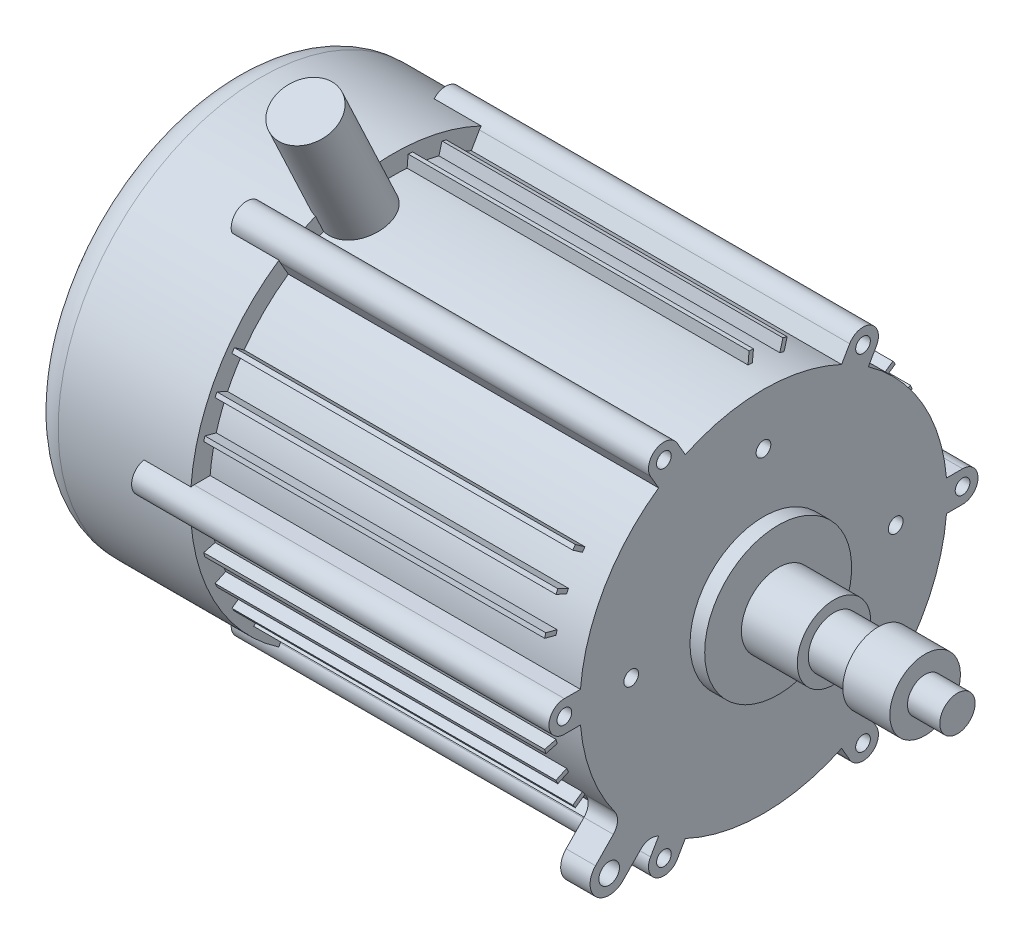
SolidWorks part; units mm, degrees
ref_plane "Спереди" through (0, 0, 0) normal (0, 0, 1) x (1, 0, 0)
ref_plane "Сверху" through (0, 0, 0) normal (0, 1, 0) x (1, 0, 0)
ref_plane "Справа" through (0, 0, 0) normal (1, 0, 0) x (0, 0, -1)
sketch "Эскиз1" plane through (0, 0, 0) normal (0, 0, 1) x (1, 0, 0)
  line L0 (-1000, 0) -> (49000, 0) construction
  line L1 (-181, 0) -> (-181, 69)
  line L2 (-181, 69) -> (-126, 69)
  line L3 (-126, 69) -> (-126, 62.5)
  line L4 (-126, 62.5) -> (0, 62.5)
  line L5 (0, 62.5) -> (0, 25)
  line L6 (0, 25) -> (5, 25)
  line L7 (5, 25) -> (5, 12.5)
  line L8 (5, 12.5) -> (24, 12.5)
  line L9 (24, 12.5) -> (24, 8.75)
  line L10 (24, 8.75) -> (39, 8.75)
  line L11 (39, 8.75) -> (39, 12)
  line L12 (39, 12) -> (55, 12)
  line L13 (55, 12) -> (55, 6)
  line L14 (55, 6) -> (66, 6)
  line L15 (66, 6) -> (66, 0)
  line L16 (-181, 0) -> (66, 0)
  point P5 (132.9582, 6.3738)
  dimension "D1" = 138
  dimension "181" = 181
  dimension "D2" = 55
  dimension "D3" = 125
  dimension "D4" = 11
  dimension "D5" = 12
  dimension "D6" = 24
  dimension "D7" = 16
  dimension "D8" = 17.5
  dimension "D9" = 15
  dimension "D10" = 25
  dimension "D11" = 50
  dimension "D12" = 5
  dimension "D13" = 50
revolve "Повернуть1" add sketch "Эскиз1" angle 360 about L0
sketch "Эскиз2" plane through (0, 0, 0) normal (1, 0, 0) x (0, 0, -1)
  line L0 (0, 0) -> (0, 62.5) construction
  line L1 (0, 0) -> (31.25, 54.1266) construction
  line L2 (19.3284, 43.9777) -> (28.4216, 38.7277)
  line L3 (19.3284, 43.9777) -> (29.3284, 61.2982)
  line L4 (28.4216, 38.7277) -> (38.4216, 56.0482)
  line L6 (0, 0) -> (62.5, 0) construction
  line L7 (47.75, 5.25) -> (67.75, 5.25)
  line L8 (47.75, -5.25) -> (67.75, -5.25)
  line L9 (47.75, 5.25) -> (47.75, -5.25)
  line L10 (0, 0) -> (31.25, -54.1266) construction
  line L11 (28.4216, -38.7277) -> (38.4216, -56.0482)
  line L12 (19.3284, -43.9777) -> (29.3284, -61.2982)
  line L13 (28.4216, -38.7277) -> (19.3284, -43.9777)
  line L14 (0, 0) -> (-31.25, -54.1266) construction
  line L15 (-19.3284, -43.9777) -> (-29.3284, -61.2982)
  line L16 (-28.4216, -38.7277) -> (-38.4216, -56.0482)
  line L17 (-19.3284, -43.9777) -> (-28.4216, -38.7277)
  line L18 (0, 0) -> (-62.5, 0) construction
  line L19 (-47.75, -5.25) -> (-67.75, -5.25)
  line L20 (-47.75, 5.25) -> (-67.75, 5.25)
  line L21 (-47.75, -5.25) -> (-47.75, 5.25)
  line L22 (0, 0) -> (-31.25, 54.1266) construction
  line L23 (-28.4216, 38.7277) -> (-38.4216, 56.0482)
  line L24 (-19.3284, 43.9777) -> (-29.3284, 61.2982)
  line L25 (-28.4216, 38.7277) -> (-19.3284, 43.9777)
  circle A0 centre (0, 0) radius 62.5 construction
  circle A1 centre (0, 0) radius 62.5 construction
  arc A2 (38.4216, 56.0482) -> (29.3284, 61.2982) centre (33.875, 58.6732) ccw
  circle A3 centre (33.875, 58.6732) radius 2.5
  arc A4 (67.75, -5.25) -> (67.75, 5.25) centre (67.75, 0) ccw
  arc A5 (29.3284, -61.2982) -> (38.4216, -56.0482) centre (33.875, -58.6732) ccw
  arc A6 (-38.4216, -56.0482) -> (-29.3284, -61.2982) centre (-33.875, -58.6732) ccw
  arc A7 (-67.75, 5.25) -> (-67.75, -5.25) centre (-67.75, 0) ccw
  arc A8 (-29.3284, 61.2982) -> (-38.4216, 56.0482) centre (-33.875, 58.6732) ccw
  circle A9 centre (67.75, 0) radius 2.5
  circle A10 centre (33.875, -58.6732) radius 2.5
  circle A11 centre (-33.875, -58.6732) radius 2.5
  circle A12 centre (-67.75, 0) radius 2.5
  circle A13 centre (-33.875, 58.6732) radius 2.5
  point P46 (0, 0)
  dimension "D5" = 5
  dimension "D1" = 30
  dimension "D2" = 20
  dimension "D3" = 10.5
  dimension "D4" = 5.25
  dimension "D6" = 6
fillet "Скругление1" radius 10 1 edges at (-181, 0, 69)
extrude "Бобышка-Вытянуть1" add sketch "Эскиз2" against normal blind 142
sketch "Эскиз3" plane through (0, 0, 0) normal (1, 0, 0) x (0, 0, -1)
  line L0 (-26.5929, -56.5603) -> (-16.2909, -60.3395) construction
  line L1 (-16.2909, -60.3395) -> (-5.4867, -62.2587) construction
  line L2 (-5.4867, -62.2587) -> (5.4867, -62.2587) construction
  line L3 (5.4867, -62.2587) -> (16.2909, -60.3395) construction
  line L4 (16.2909, -60.3395) -> (26.5929, -56.5603) construction
  line L5 (-18.0576, -64.0058) -> (-16.6094, -64.3967)
  line L6 (-18.0576, -64.0058) -> (-16.9977, -60.0802)
  line L7 (-16.6094, -64.3967) -> (-15.5496, -60.4712)
  line L8 (-16.9977, -60.0802) -> (-15.5496, -60.4712)
  line L9 (0, 0) -> (-16.2909, -60.3395) construction
  line L10 (0, 0) -> (-5.4867, -62.2587) construction
  line L11 (0, 0) -> (-5.4895, -62.2585) construction
  line L12 (-6.5879, -66.1771) -> (-5.0937, -66.3089)
  line L13 (-6.5879, -66.1771) -> (-6.2308, -62.1267)
  line L14 (-6.2308, -62.1267) -> (-4.7366, -62.2585)
  line L15 (-5.0937, -66.3089) -> (-4.7366, -62.2585)
  line L16 (0, 0) -> (5.481, -62.2592) construction
  line L17 (5.0847, -66.3096) -> (6.5789, -66.178)
  line L18 (5.0847, -66.3096) -> (4.7281, -62.2591)
  line L19 (4.7281, -62.2591) -> (6.2224, -62.1276)
  line L20 (6.5789, -66.178) -> (6.2224, -62.1276)
  line L21 (0, 0) -> (16.2827, -60.3417) construction
  line L22 (16.6007, -64.399) -> (18.0489, -64.0082)
  line L23 (16.6007, -64.399) -> (15.5414, -60.4733)
  line L24 (15.5414, -60.4733) -> (16.9896, -60.0825)
  line L25 (18.0489, -64.0082) -> (16.9896, -60.0825)
  line L26 (0, 0) -> (-16.9977, -60.0802) construction
  line L27 (0, 0) -> (-6.2308, -62.1267) construction
  line L28 (-64.4594, -16.3646) -> (-64.0739, -17.8142)
  line L29 (-64.4594, -16.3646) -> (-60.5299, -15.3196)
  line L30 (-60.5299, -15.3196) -> (-60.1444, -16.7693)
  line L31 (-64.0739, -17.8142) -> (-60.1444, -16.7693)
  line L32 (0, 0) -> (-60.401, -16.0614) construction
  line L33 (-60.605, -27.3833) -> (-59.972, -28.7431)
  line L34 (-59.972, -28.7431) -> (-56.2857, -27.0272)
  line L35 (-56.9187, -25.6674) -> (-56.2857, -27.0272)
  line L36 (-60.605, -27.3833) -> (-56.9187, -25.6674)
  line L37 (0, 0) -> (-56.661, -26.3778) construction
  line L38 (-54.8834, -37.5583) -> (-54.0224, -38.7865)
  line L39 (-54.0224, -38.7865) -> (-50.6929, -36.4525)
  line L40 (-51.5539, -35.2243) -> (-50.6929, -36.4525)
  line L41 (-54.8834, -37.5583) -> (-51.5539, -35.2243)
  line L42 (0, 0) -> (-51.1775, -35.8763) construction
  line L43 (-47.4708, -46.5761) -> (-46.4083, -47.6349)
  line L44 (-46.4083, -47.6349) -> (-43.5382, -44.7547)
  line L45 (-44.6007, -43.6959) -> (-43.5382, -44.7547)
  line L46 (-47.4708, -46.5761) -> (-44.6007, -43.6959)
  line L47 (0, 0) -> (-44.1161, -44.2721) construction
  line L48 (-46.4018, 47.6412) -> (-47.4645, 46.5826) construction
  line L49 (-46.4018, 47.6412) -> (-43.5321, 44.7606) construction
  line L50 (-43.5321, 44.7606) -> (-44.5948, 43.7019) construction
  line L51 (-47.4645, 46.5826) -> (-44.5948, 43.7019) construction
  line L52 (0, 0) -> (-44.1101, 44.2781) construction
  line L53 (-54.0171, 38.7939) -> (-54.8783, 37.5657)
  line L54 (-54.8783, 37.5657) -> (-51.5491, 35.2312)
  line L55 (-50.6879, 36.4594) -> (-51.5491, 35.2312)
  line L56 (-54.0171, 38.7939) -> (-50.6879, 36.4594)
  line L57 (0, 0) -> (-51.1743, 35.881) construction
  line L58 (-59.9681, 28.7513) -> (-60.6013, 27.3915)
  line L59 (-60.6013, 27.3915) -> (-56.9152, 25.6751)
  line L60 (-56.2821, 27.0349) -> (-56.9152, 25.6751)
  line L61 (-59.9681, 28.7513) -> (-56.2821, 27.0349)
  line L62 (0, 0) -> (-56.6586, 26.3829) construction
  line L63 (-64.0715, 17.8229) -> (-64.4572, 16.3733)
  line L64 (-64.4572, 16.3733) -> (-60.5278, 15.3278)
  line L65 (-60.1421, 16.7774) -> (-60.5278, 15.3278)
  line L66 (-64.0715, 17.8229) -> (-60.1421, 16.7774)
  line L67 (0, 0) -> (-60.3988, 16.0696) construction
  line L68 (18.0576, 64.0058) -> (16.6094, 64.3967)
  line L69 (18.0576, 64.0058) -> (16.9977, 60.0802)
  line L70 (16.9977, 60.0802) -> (15.5496, 60.4712)
  line L71 (16.6094, 64.3967) -> (15.5496, 60.4712)
  line L72 (0, 0) -> (16.2909, 60.3395) construction
  line L73 (6.5879, 66.1771) -> (5.0937, 66.3089)
  line L74 (5.0937, 66.3089) -> (4.7366, 62.2585)
  line L75 (6.2308, 62.1267) -> (4.7366, 62.2585)
  line L76 (6.5879, 66.1771) -> (6.2308, 62.1267)
  line L77 (0, 0) -> (5.4867, 62.2587) construction
  line L78 (-5.0847, 66.3096) -> (-6.5789, 66.178) construction
  line L79 (-6.5789, 66.178) -> (-6.2224, 62.1276) construction
  line L80 (-4.7281, 62.2591) -> (-6.2224, 62.1276) construction
  line L81 (-5.0847, 66.3096) -> (-4.7281, 62.2591) construction
  line L82 (0, 0) -> (-5.481, 62.2592) construction
  line L83 (-16.6007, 64.399) -> (-18.0489, 64.0082) construction
  line L84 (-18.0489, 64.0082) -> (-16.9896, 60.0825) construction
  line L85 (-15.5414, 60.4733) -> (-16.9896, 60.0825) construction
  line L86 (-16.6007, 64.399) -> (-15.5414, 60.4733) construction
  line L87 (0, 0) -> (-16.2827, 60.3417) construction
  line L88 (64.4594, 16.3646) -> (64.0739, 17.8142)
  line L89 (64.4594, 16.3646) -> (60.5299, 15.3196)
  line L90 (60.5299, 15.3196) -> (60.1444, 16.7693)
  line L91 (64.0739, 17.8142) -> (60.1444, 16.7693)
  line L92 (0, 0) -> (60.401, 16.0614) construction
  line L93 (60.605, 27.3833) -> (59.972, 28.7431)
  line L94 (59.972, 28.7431) -> (56.2857, 27.0272)
  line L95 (56.9187, 25.6674) -> (56.2857, 27.0272)
  line L96 (60.605, 27.3833) -> (56.9187, 25.6674)
  line L97 (0, 0) -> (56.661, 26.3778) construction
  line L98 (54.8834, 37.5583) -> (54.0224, 38.7865)
  line L99 (54.0224, 38.7865) -> (50.6929, 36.4525)
  line L100 (51.5539, 35.2243) -> (50.6929, 36.4525)
  line L101 (54.8834, 37.5583) -> (51.5539, 35.2243)
  line L102 (0, 0) -> (51.1775, 35.8763) construction
  line L103 (47.4708, 46.5761) -> (46.4083, 47.6349)
  line L104 (46.4083, 47.6349) -> (43.5382, 44.7547)
  line L105 (44.6007, 43.6959) -> (43.5382, 44.7547)
  line L106 (47.4708, 46.5761) -> (44.6007, 43.6959)
  line L107 (0, 0) -> (44.1161, 44.2721) construction
  line L108 (46.4018, -47.6412) -> (47.4645, -46.5826)
  line L109 (46.4018, -47.6412) -> (43.5321, -44.7606)
  line L110 (43.5321, -44.7606) -> (44.5948, -43.7019)
  line L111 (47.4645, -46.5826) -> (44.5948, -43.7019)
  line L112 (0, 0) -> (44.1101, -44.2781) construction
  line L113 (54.0171, -38.7939) -> (54.8783, -37.5657)
  line L114 (54.8783, -37.5657) -> (51.5491, -35.2312)
  line L115 (50.6879, -36.4594) -> (51.5491, -35.2312)
  line L116 (54.0171, -38.7939) -> (50.6879, -36.4594)
  line L117 (0, 0) -> (51.1743, -35.881) construction
  line L118 (59.9681, -28.7513) -> (60.6013, -27.3915)
  line L119 (60.6013, -27.3915) -> (56.9152, -25.6751)
  line L120 (56.2821, -27.0349) -> (56.9152, -25.6751)
  line L121 (59.9681, -28.7513) -> (56.2821, -27.0349)
  line L122 (0, 0) -> (56.6586, -26.3829) construction
  line L123 (64.0715, -17.8229) -> (64.4572, -16.3733)
  line L124 (64.4572, -16.3733) -> (60.5278, -15.3278)
  line L125 (60.1421, -16.7774) -> (60.5278, -15.3278)
  line L126 (64.0715, -17.8229) -> (60.1421, -16.7774)
  line L127 (0, 0) -> (60.3988, -16.0696) construction
  arc A0 (-26.5929, -56.5603) -> (26.5929, -56.5603) centre (0, 0) ccw construction
  point P14 (-16.2737, -60.2757)
  point P139 (0, 0)
  dimension "D1" = 1.5
  dimension "D2" = 4
  dimension "D3" = 10.073
  dimension "D4" = 4
  dimension "D5" = 10.07
  dimension "D6" = 6
extrude "Бобышка-Вытянуть2" add sketch "Эскиз3" against normal up to surface (142 mm away) from offset 10 up to face at (-142, 60.8503, 35.1319) offset against normal yes
sketch "Эскиз4" plane through (0, 0, 0) normal (1, 0, 0) x (0, 0, -1)
  line L0 (0, -1000) -> (0, 49000) construction
  line L1 (-57.1538, -49.3027) -> (-48.0507, -39.9672)
  line L2 (-48.0507, -39.9672) -> (-38.7432, -49.043)
  line L3 (-38.7432, -49.043) -> (-47.8462, -58.3785)
  line L4 (57.1538, -49.3027) -> (48.0507, -39.9672)
  line L5 (48.0507, -39.9672) -> (38.7432, -49.043)
  line L6 (38.7432, -49.043) -> (47.8462, -58.3785)
  arc A0 (-57.1538, -49.3027) -> (-47.8462, -58.3785) centre (-52.5, -53.8406) ccw
  circle A1 centre (0, 0) radius 25 construction
  circle A2 centre (-52.5, -53.8406) radius 3.5
  arc A3 (-62.2791, -5.25) -> (-35.6862, -51.3103) centre (0, 0) ccw construction
  circle A4 centre (52.5, -53.8406) radius 3.5
  arc A5 (57.1538, -49.3027) -> (47.8462, -58.3785) centre (52.5, -53.8406) cw
  point P13 (0, 0)
  point P16 (0, 0)
  point P17 (-38.751, -46.8671)
  dimension "D1" = 13
  dimension "D2" = 106.7001
  dimension "D4" = 7
  dimension "D3" = 118
extrude "Бобышка-Вытянуть3" add sketch "Эскиз4" against normal up to surface (10 mm away) up to face at (-10, -45.688, 45.527)
fillet "Скругление2" radius 5 4 edges at (-5, -39.9672, -48.0507) (-5, -49.043, -38.7432) (-5, -49.043, 38.7432) (-5, -39.9672, 48.0507)
sketch "Эскиз5" plane through (0, 0, 0) normal (1, 0, 0) x (0, 0, -1)
  line L0 (-1000, 0) -> (49000, 0) construction
  line L1 (0, -1000) -> (0, 49000) construction
  circle A0 centre (0, 0) radius 45 construction
  circle A1 centre (0, 45) radius 3
  circle A2 centre (-45, 0) radius 3
  circle A3 centre (45, 0) radius 3
  dimension "D1" = 90
  dimension "D2" = 6
hole_wizard "Отверстие обработанное метчиком M61" positions "Эскиз6" profile "Эскиз7" tap size "M6" standard "ISO"
sketch "Эскиз6" plane through (0, 0, 0) normal (1, 0, 0) x (0, 0, -1)
  point P0 (0, 45)
  point P3 (45, 0)
  point P6 (-45, 0)
sketch "Эскиз7" plane through (0, 45, 0) normal (0, 1, 0) x (0, 0, -1)
  line L0 (0, 0) -> (0, 16.5022)
  line L1 (0, 16.5022) -> (2.5, 15)
  line L2 (2.5, 15) -> (2.5, 0)
  line L5 (2.5, 0) -> (0, 0)
  line L10 (0, 16.5022) -> (-2.5, 15) construction
  line L11 (0, -6.35) -> (0, 107.95) construction
  dimension "Диаметр сверла" = 5
  dimension "Глубина сверла" = 15
  dimension "Угол заточки сверла" = 118
cosmetic thread "Отверстие резьбы1" parameters "D1"=10, "D2"=6
cosmetic thread "Отверстие резьбы2" parameters "D1"=10, "D2"=6
cosmetic thread "Отверстие резьбы3" parameters "D1"=10, "D2"=6
ref_plane "Плоскость1" through (0, 56.5603, 26.5929) normal (0, 0.905, 0.4255) x (1, 0, 0)
sketch "Эскиз8" plane through (0, 56.5603, 26.5929) normal (0, 0.905, 0.4255) x (1, 0, 0)
  line L0 (-126, 0) -> (0, 0) construction
  line L1 (0, -181897.8961) -> (0, 225336.1997) construction
  circle A0 centre (-124, 13) radius 10
  point P2 (-114.0251, 14.2246)
  dimension "D1" = 20
  dimension "D2" = 3
  dimension "D3" = 114
extrude "Бобышка-Вытянуть4" add sketch "Эскиз8" along normal blind 40 and the other way blind 10
equation "\"D4@Эскиз2\"=\"D3@Эскиз2\"/2"
